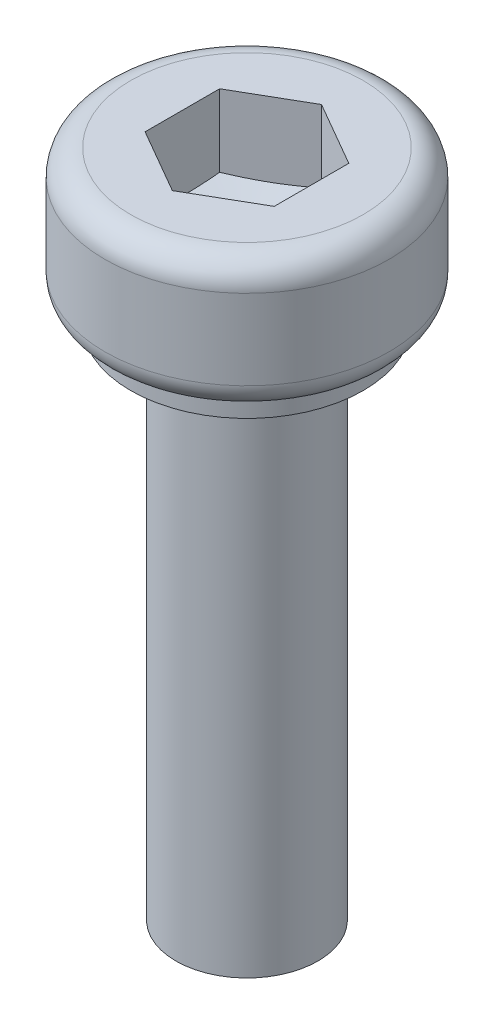
SolidWorks part; units mm, degrees
ref_plane "Front Plane" through (0, 0, 0) normal (0, 0, 1) x (1, 0, 0)
ref_plane "Top Plane" through (0, 0, 0) normal (0, 1, 0) x (1, 0, 0)
ref_plane "Right Plane" through (0, 0, 0) normal (1, 0, 0) x (0, 0, -1)
sketch "Sketch1" plane through (0, 0, 0) normal (0, 0, 1) x (1, 0, 0)
  line L0 (0, 4.0942) -> (0, -5.2249) construction
  line L1 (0, 6.475) -> (2.25, 6.475)
  line L2 (2.75, 5.975) -> (2.75, 4.425)
  line L3 (2.25, 3.525) -> (1.375, 3.525)
  line L4 (1.375, 3.525) -> (1.375, -6.475)
  line L5 (1.375, -6.475) -> (0, -6.475)
  line L6 (0, -6.475) -> (0, 6.475)
  line L7 (2.25, 3.525) -> (2.25, 3.925)
  line L8 (2.75, 3.525) -> (2.25, 3.525) construction
  line L9 (2.75, 4.425) -> (2.75, 3.525) construction
  line L10 (2.75, 6.475) -> (2.75, 5.975) construction
  line L11 (2.25, 6.475) -> (2.75, 6.475) construction
  arc A0 (2.25, 3.925) -> (2.75, 4.425) centre (2.25, 4.425) ccw
  arc A1 (2.25, 6.475) -> (2.75, 5.975) centre (2.25, 5.975) cw
  point P5 (0, 0)
  dimension "D5" = 0.5
  dimension "D1" = 10
  dimension "D2" = 1.375
  dimension "D3" = 2.95
  dimension "D4" = 2.75
  dimension "D6" = 0.4
revolve "Revolve1" add sketch "Sketch1" angle 360 about L0
sketch "Sketch2" plane through (0, 6.475, 0) normal (0, 1, 0) x (1, 0, 0)
  line L1 (0, 1.4434) -> (-1.25, 0.7217)
  line L2 (-1.25, 0.7217) -> (-1.25, -0.7217)
  line L3 (-1.25, -0.7217) -> (0, -1.4434)
  line L4 (0, -1.4434) -> (1.25, -0.7217)
  line L5 (1.25, -0.7217) -> (1.25, 0.7217)
  line L6 (1.25, 0.7217) -> (0, 1.4434)
  circle A0 centre (0, 0) radius 1.25 construction
  dimension "D1" = 2.5
extrude "Boss-Extrude1" add sketch "Sketch2" against normal blind 2 separate body
sketch "Sketch3" plane through (0, 0, 0) normal (1, 0, 0) x (0, 0, -1)
  line L0 (0, 4.875) -> (0.4, 4.875)
  line L1 (0.4, 4.875) -> (1.4434, 5.075)
  line L2 (1.4434, 4.475) -> (1.4434, 6.475) construction
  line L3 (1.4434, 5.075) -> (1.4434, 4.475)
  line L4 (1.4434, 4.475) -> (0, 4.475)
  line L5 (-0.7217, 4.475) -> (0.7217, 4.475) construction
  line L6 (0, 4.475) -> (0, 4.875)
  line L7 (-0.7217, 6.475) -> (0.7217, 6.475) construction
  dimension "D1" = 1.6
  dimension "D2" = 1.4
  dimension "D3" = 0.4
revolve "Cut-Revolve1" cut sketch "Sketch3" angle 360 about L6
combine bodies "Combine1" operation type subtract main body 101 bodies to subtract 104
equation "\"Length\"= 10mm"
equation "\"D1@Sketch1\"=\"Length\""
equation "\"ThreadDiam\"= 2.75"
equation "\"D2@Sketch1\"=\"ThreadDiam\"/2"
equation "\"HeadHeight\"=2.95"
equation "\"D3@Sketch1\"=\"HeadHeight\""
equation "\"HeadDiam\"= 5.5"
equation "\"D4@Sketch1\"=\"HeadDiam\"/2"
equation "\"HexSize\"=2.5"
equation "\"D1@Sketch2\"=\"HexSize\""
